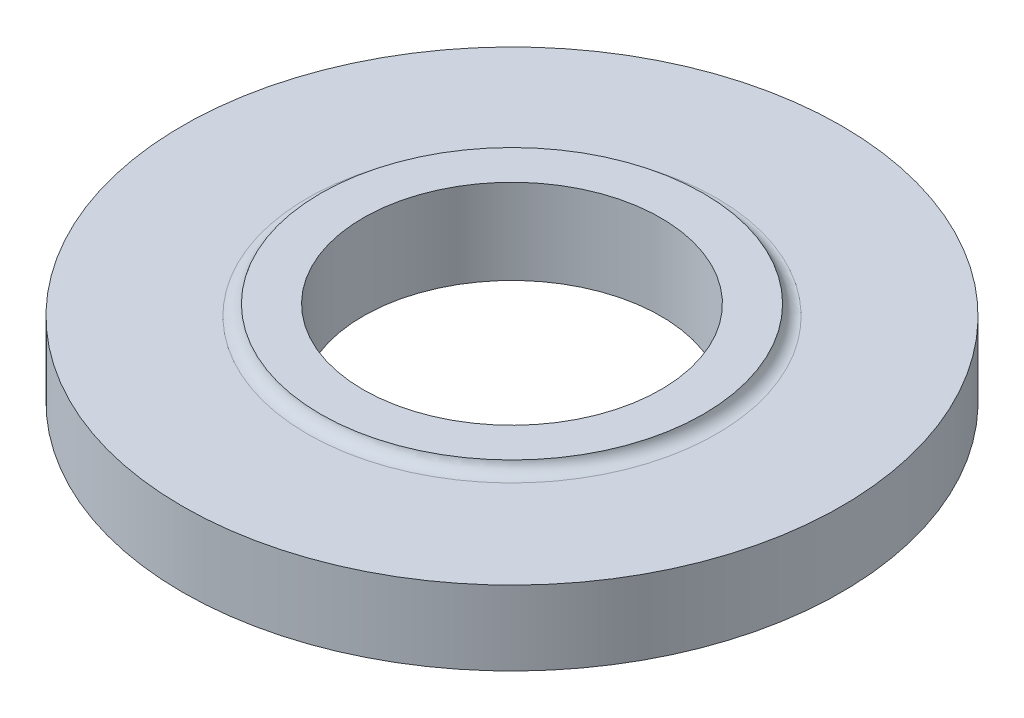
SolidWorks part; units mm, degrees
ref_plane "Front Plane" through (0, 0, 0) normal (0, 0, 1) x (1, 0, 0)
ref_plane "Top Plane" through (0, 0, 0) normal (0, 1, 0) x (1, 0, 0)
ref_plane "Right Plane" through (0, 0, 0) normal (1, 0, 0) x (0, 0, -1)
sketch "Sketch1" plane through (0, 0, 0) normal (0, 1, 0) x (1, 0, 0)
  circle A0 centre (0, 0) radius 24.6062
extrude "Boss-Extrude1" add sketch "Sketch1" along normal blind 5.5562
sketch "Sketch2" plane through (0, 5.5562, 0) normal (0, 1, 0) x (1, 0, 0)
  circle A0 centre (0, 0) radius 14.2875
extrude "Boss-Extrude2" add sketch "Sketch2" along normal blind 0.7938
sketch "Sketch3" plane through (0, 6.35, 0) normal (0, 1, 0) x (1, 0, 0)
  circle A0 centre (0, 0) radius 11.1125
extrude "Cut-Extrude1" cut sketch "Sketch3" against normal through all
fillet "Fillet1" radius 1 1 edges at (0, 5.5562, 14.2875)
ref_plane "Plane1" through (0, 5.5562, 0) normal (-1, 0, 0) x (0, 0, -1)
sketch "Sketch5" plane through (0, 5.5562, 0) normal (-1, 0, 0) x (0, 0, -1)
  line L0 (21.7196, 6.7707) -> (25.4889, 7.1005)
  line L1 (25.4889, 7.1005) -> (25.4889, -0.6965)
  line L2 (25.4889, -0.6965) -> (21.7196, -0.3667)
  line L3 (21.082, 0.3292) -> (21.082, 6.0749)
  line L4 (0, 50) -> (0, -50) construction
  arc A0 (21.7196, -0.3667) -> (21.082, 0.3292) centre (21.7805, 0.3292) cw
  arc A1 (21.082, 6.0749) -> (21.7196, 6.7707) centre (21.7805, 6.0749) cw
